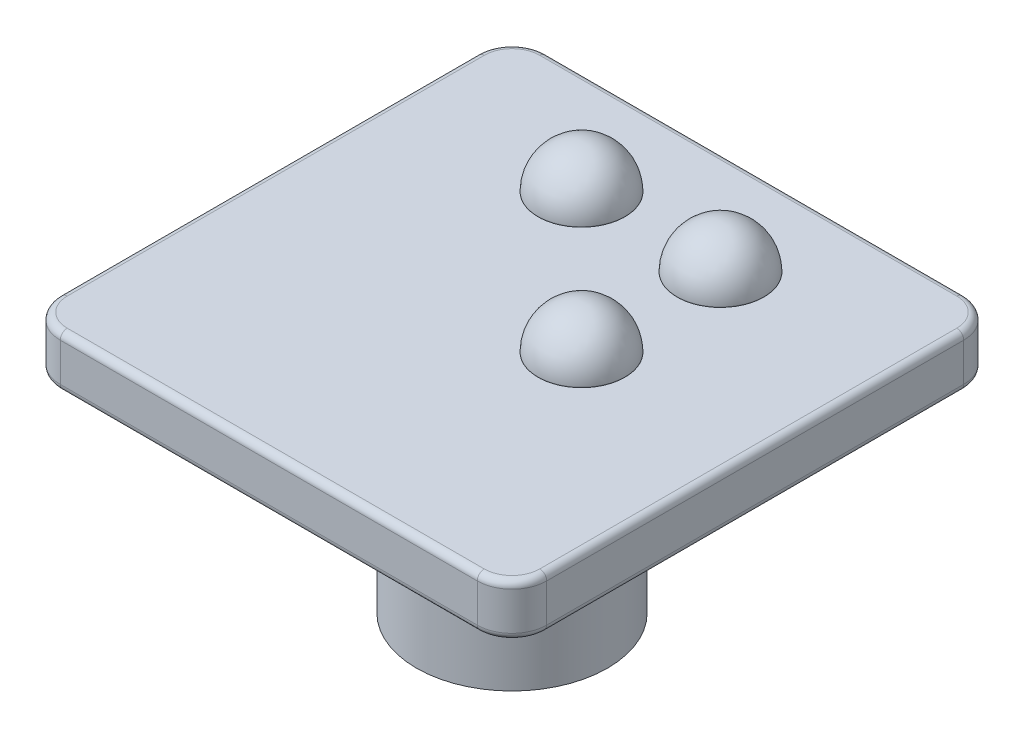
SolidWorks part; units mm, degrees
ref_plane "Front Plane" through (0, 0, 0) normal (0, 0, 1) x (1, 0, 0)
ref_plane "Top Plane" through (0, 0, 0) normal (0, 1, 0) x (1, 0, 0)
ref_plane "Right Plane" through (0, 0, 0) normal (1, 0, 0) x (0, 0, -1)
sketch "Sketch1" plane through (0, 0, 0) normal (0, 1, 0) x (1, 0, 0)
  line L1 (-7.3247, 4.3967) -> (4.6753, 4.3967)
  line L2 (-8.3247, 3.3967) -> (-8.3247, -8.6033)
  line L3 (-7.3247, -9.6033) -> (4.6753, -9.6033)
  line L4 (5.6753, 3.3967) -> (5.6753, -8.6033)
  arc A0 (-8.3247, -8.6033) -> (-7.3247, -9.6033) centre (-7.3247, -8.6033) ccw
  arc A1 (4.6753, -9.6033) -> (5.6753, -8.6033) centre (4.6753, -8.6033) ccw
  arc A2 (4.6753, 4.3967) -> (5.6753, 3.3967) centre (4.6753, 3.3967) cw
  arc A3 (-7.3247, 4.3967) -> (-8.3247, 3.3967) centre (-7.3247, 3.3967) ccw
  point P8 (5.6753, -9.6033)
  point P11 (5.6753, 4.3967)
  point P14 (-8.3247, 4.3967)
  dimension "D3" = 1
  dimension "D1" = 14
  dimension "D2" = 14
extrude "Boss-Extrude1" add sketch "Sketch1" along normal blind 1.5
sketch "Sketch2" plane through (0, 0, 0) normal (0, -1, 0) x (1, 0, 0)
  line L0 (-7.3247, 9.6033) -> (4.6753, 9.6033) construction
  line L1 (5.6753, 8.6033) -> (5.6753, -3.3967) construction
  line L2 (-1.3247, -4.3967) -> (-1.3247, 9.6033) construction
  line L3 (-8.3247, 2.6033) -> (5.6753, 2.6033) construction
  line L4 (-8.3247, -3.3967) -> (-8.3247, 8.6033) construction
  circle A0 centre (-1.3247, 2.6033) radius 2.75
  dimension "D1" = 7
  dimension "D2" = 7
extrude "Boss-Extrude2" add sketch "Sketch2" along normal blind 6
sketch "Sketch3" plane through (0, -6, 0) normal (0, -1, 0) x (1, 0, 0)
  line L0 (-1.3247, 5.3533) -> (-1.3247, -0.1467) construction
  line L1 (-3.3247, 3.1533) -> (0.6753, 3.1533)
  line L2 (-3.3247, 3.1533) -> (-3.3247, 2.0533)
  line L3 (-3.3247, 2.0533) -> (0.6753, 2.0533)
  line L4 (0.6753, 3.1533) -> (0.6753, 2.0533)
  line L5 (-1.8747, 4.6033) -> (-0.7747, 4.6033)
  line L6 (-1.8747, 4.6033) -> (-1.8747, 0.6033)
  line L7 (-1.8747, 0.6033) -> (-0.7747, 0.6033)
  line L8 (-0.7747, 4.6033) -> (-0.7747, 0.6033)
  line L9 (-4.0747, 2.6033) -> (1.4253, 2.6033) construction
  circle A3 centre (-1.3247, 2.6033) radius 2.75 construction
  circle A4 centre (-1.3247, 2.6033) radius 2.75 construction
  dimension "D7" = 0.55
  dimension "D1" = 4
  dimension "D2" = 1.1
  dimension "D3" = 1.1
  dimension "D4" = 4
  dimension "D5" = 2
  dimension "D6" = 2
  dimension "D8" = 0.55
extrude "Cut-Extrude1" cut sketch "Sketch3" against normal blind 6 contours L8 L5 L6 L1 | L1 L8 L3 L4 | L8 L1 L6 L3 | L6 L1 L2 L3 | L8 L3 L6 L7 region at (-2.5997, -6, 2.6033) region at (-1.3247, -6, 3.8783) region at (-1.3247, -6, 2.6033) region at (-0.0497, -6, 2.6033) region at (-1.3247, -6, 1.3283)
chamfer "Chamfer1" distance 0.3 angle 45 12 edges at (-1.3247, -6, 0.6033) (-1.8747, -6, 1.3283) (-2.5997, -6, 2.0533) (-3.3247, -6, 2.6033) (-2.5997, -6, 3.1533) (-0.7747, -6, 1.3283) (-0.0497, -6, 2.0533) (0.6753, -6, 2.6033) (-0.0497, -6, 3.1533) (-0.7747, -6, 3.8783) (-1.3247, -6, 4.6033) (-1.8747, -6, 3.8783)
fillet "Fillet1" radius 1 1 edges at (-1.3247, 0, -0.1467)
sketch "Sketch4" plane through (0, 1.5, 0) normal (0, 1, 0) x (1, 0, 0)
  line L0 (-1.3247, 4.3967) -> (-1.3247, -9.6033) construction
  line L1 (4.6753, 4.3967) -> (-7.3247, 4.3967) construction
  line L2 (-7.3247, -9.6033) -> (4.6753, -9.6033) construction
  line L3 (5.6753, -2.6033) -> (-8.3247, -2.6033) construction
  line L4 (-8.3247, 3.3967) -> (-8.3247, -8.6033) construction
  line L5 (5.6753, -8.6033) -> (5.6753, 3.3967) construction
  line L6 (-3.3247, 4.3967) -> (-3.3247, -9.6033) construction
  line L7 (0.6753, 4.3967) -> (0.6753, -9.6033) construction
  line L8 (-8.3247, 1.3967) -> (5.6753, 1.3967) construction
  line L9 (5.6753, -6.6033) -> (-8.3247, -6.6033) construction
  circle A0 centre (-3.3247, 1.3967) radius 1.25
  circle A1 centre (0.6753, -2.6033) radius 1.25
  circle A5 centre (0.6753, 1.3967) radius 1.25
  dimension "D1" = 4
  dimension "D2" = 4
  dimension "D3" = 2
  dimension "D4" = 2
extrude "Boss-Extrude3" add sketch "Sketch4" along normal blind 0.01
dome "Dome1" faces to dome 1 distance 1.25 reverse direction no elliptical dome no face at (-3.3247, 1.51, -0.1467) parameters "D1"=1.25
dome "Dome2" faces to dome 1 distance 1.25 reverse direction no elliptical dome no face at (0.6753, 1.51, -0.1467) parameters "D1"=1.25
dome "Dome4" faces to dome 1 distance 1.25 reverse direction no elliptical dome no face at (0.6753, 1.51, 3.8533) parameters "D1"=1.25
fillet "Fillet3" radius 0.2 16 edges at (5.3824, 1.5, -4.1038) (5.6753, 1.5, 2.6033) (5.3824, 1.5, 9.3104) (-1.3247, 1.5, 9.6033) (-8.0318, 1.5, 9.3104) (-8.0318, 1.5, -4.1038) (-8.3247, 1.5, 2.6033) (-1.3247, 1.5, -4.3967) (5.3824, 0, 9.3104) (5.6753, 0, 2.6033) (5.3824, 0, -4.1038) (-1.3247, 0, -4.3967) (-8.0318, 0, -4.1038) (-8.3247, 0, 2.6033) (-8.0318, 0, 9.3104) (-1.3247, 0, 9.6033)
